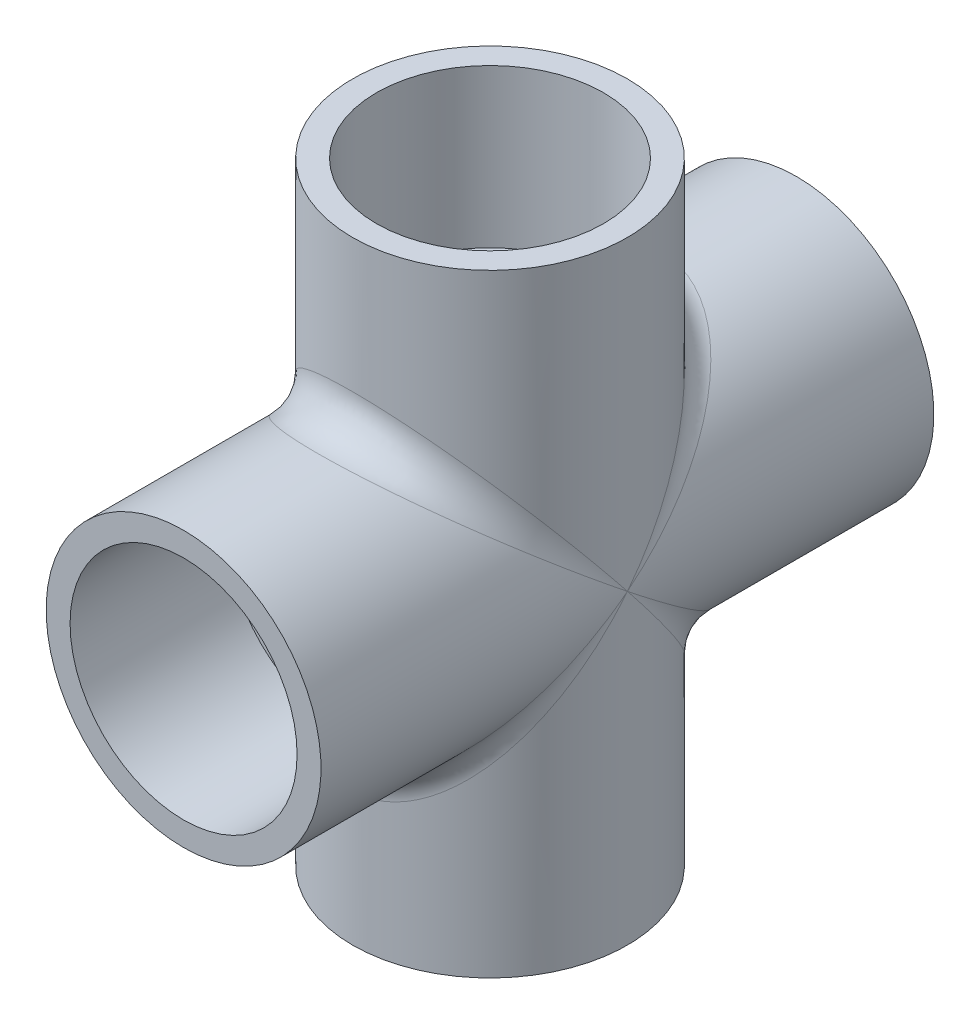
SolidWorks part; units mm, degrees
ref_plane "Front Plane" through (0, 0, 0) normal (0, 0, 1) x (1, 0, 0)
ref_plane "Top Plane" through (0, 0, 0) normal (0, 1, 0) x (1, 0, 0)
ref_plane "Right Plane" through (0, 0, 0) normal (1, 0, 0) x (0, 0, -1)
sketch "Sketch1" plane through (0, 0, 0) normal (1, 0, 0) x (0, 0, -1)
  line L0 (0, 0) -> (-65.4844, 0) construction
  line L1 (0, 0) -> (65.4844, 0) construction
  line L2 (0, 0) -> (0, 65.4844) construction
  line L3 (-31.75, -20.447) -> (-31.75, 20.447) construction
  line L4 (-20.447, 31.75) -> (20.447, 31.75) construction
  line L5 (31.75, -20.447) -> (31.75, 20.447) construction
  line L6 (-65.4844, -29.3688) -> (-65.4844, 29.3687) construction
  line L7 (65.4844, -29.3687) -> (65.4844, 29.3688) construction
  line L8 (29.3687, 65.4844) -> (-29.3688, 65.4844) construction
  line L9 (-31.75, 20.447) -> (-65.4844, 20.447) construction
  line L10 (-20.447, 31.75) -> (-20.447, 65.4844) construction
  line L11 (31.75, 20.447) -> (65.4844, 20.447) construction
  line L12 (-48.6172, -24.257) -> (-48.6172, 24.257) construction
  line L13 (-24.257, 48.6172) -> (24.257, 48.6172) construction
  line L14 (48.6172, -24.257) -> (48.6172, 24.257) construction
  line L15 (0, 0) -> (0, -65.4844) construction
  line L16 (-29.3687, -65.4844) -> (29.3688, -65.4844) construction
  line L17 (-20.447, -31.75) -> (20.447, -31.75) construction
  line L18 (-24.257, -48.6172) -> (24.257, -48.6172) construction
  line L19 (20.447, -31.75) -> (20.447, -65.4844) construction
  point P4 (0, 0)
  point P10 (-31.75, 0)
  point P13 (0, 31.75)
  point P16 (31.75, 0)
  point P19 (-65.4844, 0)
  point P22 (65.4844, 0)
  point P25 (0, 65.4844)
  point P27 (-48.6172, 20.447)
  point P31 (-48.6172, 0)
  point P34 (0, 48.6172)
  point P37 (48.6172, 0)
  point P38 (-20.447, 48.6172)
  point P39 (48.6172, 20.447)
  point P42 (0, -65.4844)
  point P46 (0, -31.75)
  point P49 (0, -48.6172)
  point P50 (20.447, -48.6172)
  dimension "Horz Leg Length" = 65.4844
  dimension "Vert Leg Length" = 65.4844
  dimension "Horz Length" = 130.9688
  dimension "Horz Center to Socket" = 31.75
  dimension "D1" = 31.75
  dimension "Vert Center to Socket" = 31.75
  dimension "Pipe ID" = 40.894
  dimension "Tee OD" = 58.7375
  dimension "For Pipe OD" = 48.514
  dimension "D2" = 31.75
  dimension "Vert Length" = 130.9688
sketch "Sketch2" plane through (0, 0, 0) normal (1, 0, 0) x (0, 0, -1)
  line L0 (-65.4844, 29.3687) -> (65.4844, 29.3688)
  line L1 (65.4844, 29.3688) -> (65.4844, 0)
  line L2 (65.4844, -29.3687) -> (65.4844, 29.3688) construction
  line L8 (-65.4844, -29.3688) -> (-65.4844, 29.3687) construction
  line L9 (-65.4844, 0) -> (-65.4844, 29.3687)
  line L10 (-65.4844, 0) -> (65.4844, 0)
revolve "Revolve1" add sketch "Sketch2" angle 360 about L0
sketch "Sketch3" plane through (0, 0, 0) normal (1, 0, 0) x (0, 0, -1)
  line L0 (0, 65.4844) -> (29.3687, 65.4844)
  line L1 (29.3687, 65.4844) -> (29.3688, -65.4844)
  line L3 (29.3688, -65.4844) -> (0, -65.4844)
  line L4 (0, -65.4844) -> (0, 65.4844)
revolve "Revolve2" add sketch "Sketch3" angle 360 about L2
sketch "Sketch4" plane through (0, 0, 0) normal (1, 0, 0) x (0, 0, -1)
  line L0 (-65.4844, 24.257) -> (-31.75, 24.257)
  line L1 (-65.4844, -29.3688) -> (-65.4844, 29.3687) construction
  line L2 (-31.75, 24.257) -> (-31.75, 20.447)
  line L3 (-31.75, 20.447) -> (31.75, 20.447)
  line L4 (31.75, 20.447) -> (31.75, 24.257)
  line L5 (31.75, 24.257) -> (65.4844, 24.257)
  line L6 (65.4844, -29.3687) -> (65.4844, 29.3688) construction
  line L7 (65.4844, 24.257) -> (65.4844, 0)
  line L8 (65.4844, 0) -> (-65.4844, 0)
  line L9 (-65.4844, 0) -> (-65.4844, 24.257)
revolve "Cut-Revolve1" cut sketch "Sketch4" angle 360 about L8
sketch "Sketch5" plane through (0, 0, 0) normal (1, 0, 0) x (0, 0, -1)
  line L0 (0, 65.4844) -> (0, -65.4844)
  line L1 (29.3687, 65.4844) -> (-29.3688, 65.4844) construction
  line L3 (0, -65.4844) -> (-24.257, -65.4844)
  line L5 (-20.447, -31.75) -> (-20.447, 31.75)
  line L6 (-20.447, 31.75) -> (-24.257, 31.75)
  line L7 (-24.257, 31.75) -> (-24.257, 65.4844)
  line L8 (-24.257, 65.4844) -> (0, 65.4844)
  line L9 (-29.3687, -65.4844) -> (29.3688, -65.4844) construction
  line L10 (-24.257, -65.4844) -> (-24.257, -31.75)
  line L11 (-24.257, -31.75) -> (-20.447, -31.75)
revolve "Cut-Revolve2" cut sketch "Sketch5" angle 360 about L0
fillet "Fillet1" radius 7.579 4 edges at (0, -29.3687, -29.3687) (0, -29.3688, 29.3687) (0, 29.3687, 29.3687) (0, 29.3688, -29.3687)
sketch "Sketch6" plane through (0, 0, 0) normal (1, 0, 0) x (0, 0, -1)
  line L0 (-65.4844, 24.257) -> (-31.75, 24.257)
  line L1 (-65.4844, -29.3688) -> (-65.4844, 29.3687) construction
  line L2 (-31.75, 24.257) -> (-31.75, 20.447)
  line L3 (-31.75, 20.447) -> (-20.447, 20.447)
  line L4 (-20.447, 20.447) -> (-20.447, 31.75)
  line L5 (-20.447, 31.75) -> (-24.257, 31.75)
  line L6 (-24.257, 31.75) -> (-24.257, 65.4844)
  line L7 (29.3687, 65.4844) -> (-29.3688, 65.4844) construction
  line L8 (-31.75, -20.447) -> (-20.447, -20.447)
  line L9 (31.75, -20.447) -> (31.75, -24.257)
  line L10 (31.75, -24.257) -> (65.4844, -24.257)
  line L11 (65.4844, -29.3687) -> (65.4844, 29.3688) construction
  line L12 (-31.75, -20.447) -> (-31.75, -24.257)
  line L13 (-31.75, -24.257) -> (-65.4844, -24.257)
  line L14 (65.4844, 24.257) -> (31.75, 24.257)
  line L15 (31.75, 24.257) -> (31.75, 20.447)
  line L16 (31.75, 20.447) -> (20.447, 20.447)
  line L17 (20.447, 20.447) -> (20.447, 31.75)
  line L18 (20.447, 31.75) -> (24.257, 31.75)
  line L19 (24.257, 31.75) -> (24.257, 65.4844)
  line L20 (-20.447, -31.75) -> (-20.447, -20.447)
  line L21 (20.447, -31.75) -> (20.447, -20.447)
  line L22 (24.257, -65.4844) -> (24.257, -31.75)
  line L23 (-29.3687, -65.4844) -> (29.3688, -65.4844) construction
  line L24 (24.257, -31.75) -> (20.447, -31.75)
  line L25 (-24.257, -65.4844) -> (-24.257, -31.75)
  line L26 (-24.257, -31.75) -> (-20.447, -31.75)
  line L27 (20.447, -20.447) -> (31.75, -20.447)
sketch "Sketch7" plane through (0, 0, 65.4844) normal (0, 0, 1) x (1, 0, 0)
  circle A0 centre (0, 0) radius 24.257 construction
  circle A1 centre (0, 0) radius 24.257
  point P3 (0, -24.257)
  point P4 (24.257, 0)
  point P5 (-24.257, 0)
  point P6 (0, 24.257)
ref_axis "Axis1" through (32.3056, 0, 0) along (-1, 0, 0)
equation "\"D1@Fillet1\"=\"Tee OD@Sketch1\"*0.1290322581"
equation "\"D2@Sketch1\"=\"Vert Center to Socket@Sketch1\""
equation "\"Horz Leg Length@Sketch1\" = \"Horz Length@Sketch1\" / 2"
equation "\"Vert Leg Length@Sketch1\"=\"Vert Length@Sketch1\"/2"
equation "\"D1@Sketch1\"=\"Horz Center to Socket@Sketch1\""
